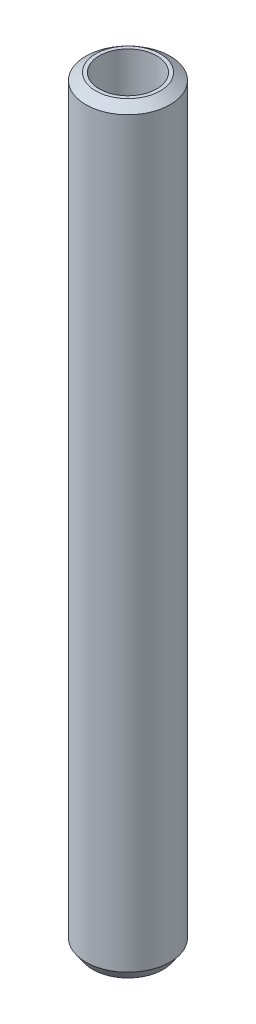
SolidWorks part; units mm, degrees
ref_plane "Front Plane" through (0, 0, 0) normal (0, 0, 1) x (1, 0, 0)
ref_plane "Top Plane" through (0, 0, 0) normal (0, 1, 0) x (1, 0, 0)
ref_plane "Right Plane" through (0, 0, 0) normal (1, 0, 0) x (0, 0, -1)
sketch "Sketch1" plane through (0, 0, 0) normal (0, 1, 0) x (1, 0, 0)
  circle A0 centre (0, 0) radius 30
  dimension "SHAFT_OD" = 60
extrude "Boss-Extrude1" add sketch "Sketch1" along normal blind 540.8454
sketch "Sketch2" plane through (0, 0, 0) normal (0, 1, 0) x (1, 0, 0)
  circle A0 centre (0, 0) radius 20.4521
  dimension "BORE_D" = 40.9042
extrude "Cut-Extrude1" cut sketch "Sketch2" along normal through all
chamfer "Chamfer1" distance 4.9574 angle 54.924 2 edges at (0, 540.8454, 30) (0, 0, 30) first distance on face at (0, 540.8454, 30) first distance on face at (0, 0, 20.4521)
